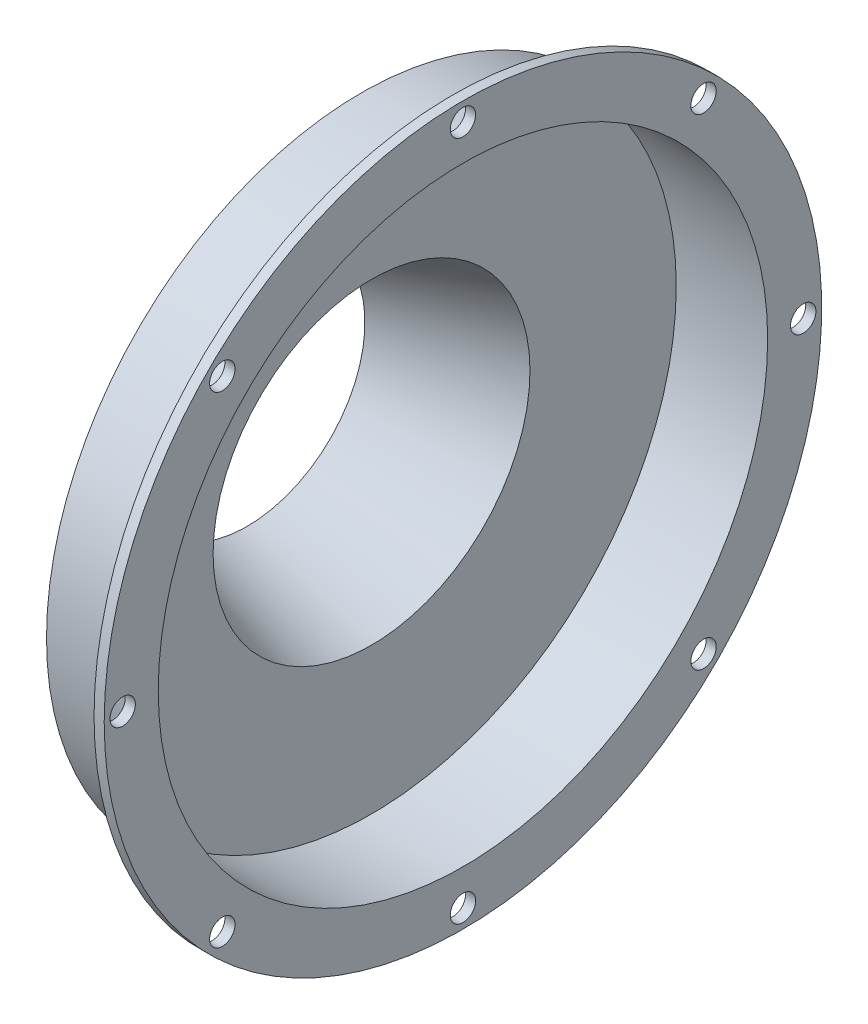
SolidWorks part; units mm, degrees
ref_plane "Front Plane" through (0, 0, 0) normal (0, 0, 1) x (1, 0, 0)
ref_plane "Top Plane" through (0, 0, 0) normal (0, 1, 0) x (1, 0, 0)
ref_plane "Right Plane" through (0, 0, 0) normal (1, 0, 0) x (0, 0, -1)
sketch "Sketch1" plane through (0, 0, 0) normal (0, 0, 1) x (1, 0, 0)
  line L0 (0, 0) -> (61.3012, 0) construction
  line L1 (0, 29.464) -> (31.115, 39.624)
  line L2 (31.115, 39.624) -> (31.115, 76.2)
  line L3 (31.115, 76.2) -> (53.975, 76.2)
  line L4 (53.975, 76.2) -> (53.975, 89.7128)
  line L5 (-0.7884, 31.8785) -> (28.575, 41.4666)
  line L6 (28.575, 41.4666) -> (28.575, 78.74)
  line L7 (28.575, 78.74) -> (51.435, 78.74)
  line L8 (51.435, 78.74) -> (51.435, 89.7128)
  line L9 (-0.7884, 31.8785) -> (0, 29.464)
  line L10 (51.435, 89.7128) -> (53.975, 89.7128)
  point P5 (30.6506, 0)
  dimension "D1" = 29.464
  dimension "D2" = 39.624
  dimension "D3" = 31.115
  dimension "D4" = 76.2
  dimension "D5" = 89.7128
  dimension "D7" = 22.86
  dimension "D6" = 2.54
revolve "Revolve1" add sketch "Sketch1" angle 360 about L0
sketch "Sketch2" plane through (51.435, 0, 0) normal (-1, 0, 0) x (0, 0, 1)
  circle A0 centre (0, 85.09) radius 3.175
  dimension "D1" = 6.35
  dimension "D2" = 85.09
extrude "Cut-Extrude1" cut sketch "Sketch2" against normal blind 2.54
pattern_circular "CirPattern1" count 8 over 360 about axis through (51.435, 0, 0) along (-1, 0, 0) of "Cut-Extrude1"
